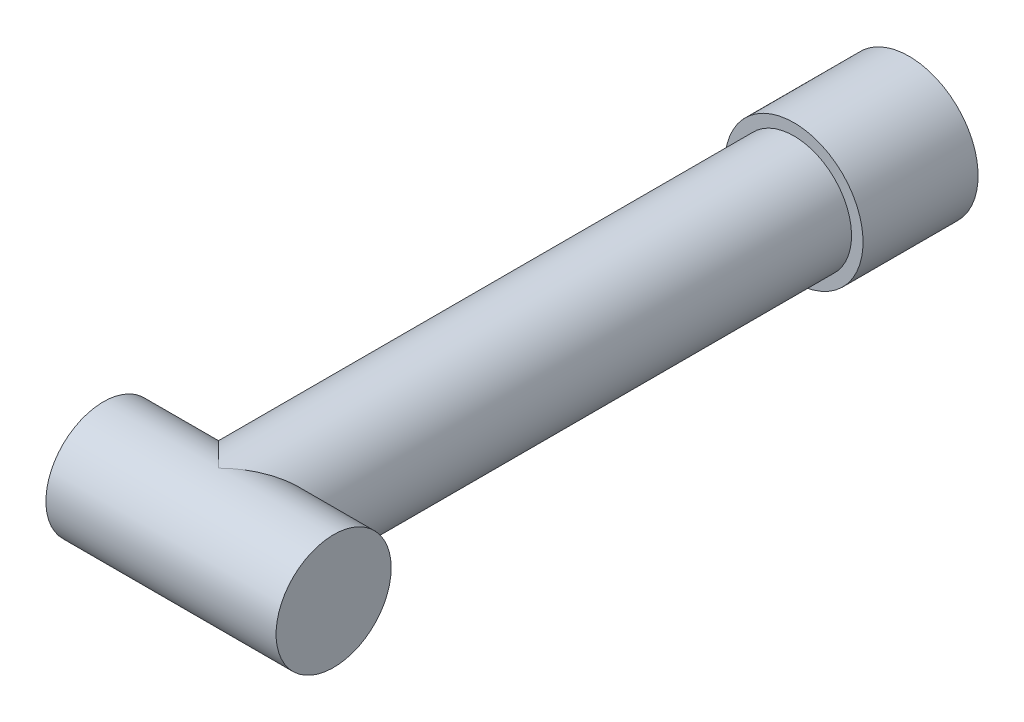
SolidWorks part; units mm, degrees
ref_plane "Front Plane" through (0, 0, 0) normal (0, 0, 1) x (1, 0, 0)
ref_plane "Top Plane" through (0, 0, 0) normal (0, 1, 0) x (1, 0, 0)
ref_plane "Right Plane" through (0, 0, 0) normal (1, 0, 0) x (0, 0, -1)
sketch "Sketch1" plane through (0, 0, 0) normal (0, 0, 1) x (1, 0, 0)
  circle A0 centre (0, 0) radius 2.5
  dimension "D1" = 5
extrude "Boss-Extrude1" add sketch "Sketch1" against normal blind 30
sketch "Sketch2" plane through (0, 0, 0) normal (1, 0, 0) x (0, 0, -1)
  circle A0 centre (0, 0) radius 2.5
extrude "Boss-Extrude2" add sketch "Sketch2" along normal blind 5 and the other way blind 5
sketch "Sketch3" plane through (0, 0, -30) normal (0, 0, -1) x (-1, 0, 0)
  circle A0 centre (0, 0) radius 3
  dimension "D1" = 6
extrude "Boss-Extrude3" add sketch "Sketch3" against normal blind 5
sketch3d "3DSketch1"
  line L0 (0, -2.5, 0) -> (0, -2.5, -25) construction
  circle A0 centre (0, 0, -25) radius 2.5 construction
  spline S0 degree 3 poles (0, 2.5, 0) (-5, 2.5, -5) (-5, -2.5, -5) (0, -2.5, 0) knots 0 0 0 0 1 1 1 1 weights 1 0.333333 0.333333 1 construction
  spline S1 degree 3 poles (0, -2.5, 0) (5, -2.5, -5) (5, 2.5, -5) (0, 2.5, 0) knots 0 0 0 0 1 1 1 1 weights 1 0.333333 0.333333 1 construction
  point P8 (0, 0, -22.5)
